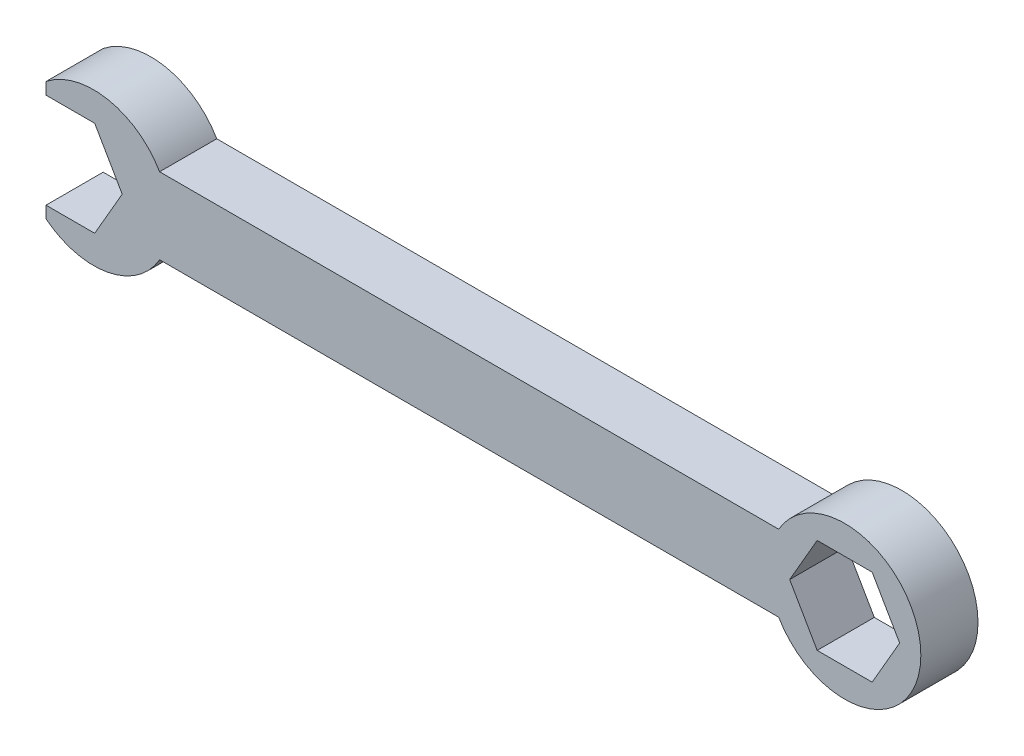
SolidWorks part; units mm, degrees
ref_plane "Front Plane" through (0, 0, 0) normal (0, 0, 1) x (1, 0, 0)
ref_plane "Top Plane" through (0, 0, 0) normal (0, 1, 0) x (1, 0, 0)
ref_plane "Right Plane" through (0, 0, 0) normal (1, 0, 0) x (0, 0, -1)
sketch "Sketch1" plane through (0, 0, 0) normal (0, 0, 1) x (1, 0, 0)
  line L0 (4.9888, 5.08) -> (87.5388, 5.08)
  line L1 (87.5388, -5.08) -> (4.9888, -5.08)
  line L2 (-10.16, 6.35) -> (-10.16, 7.9311)
  line L3 (103.67, 0) -> (100.0038, 6.35)
  line L4 (100.0038, 6.35) -> (92.6715, 6.35)
  line L5 (92.6715, 6.35) -> (89.0053, 0)
  line L6 (89.0053, 0) -> (92.6715, -6.35)
  line L7 (92.6715, -6.35) -> (100.0038, -6.35)
  line L8 (100.0038, -6.35) -> (103.67, 0)
  line L10 (-10.16, -6.35) -> (-3.6662, -6.35)
  line L11 (-3.6662, -6.35) -> (0, 0)
  line L12 (0, 0) -> (-3.6662, 6.35)
  line L13 (-3.6662, 6.35) -> (-10.16, 6.35)
  line L15 (-10.16, -6.35) -> (-10.16, -7.9311)
  line L17 (-12.8235, 3.1891) -> (-14.6472, 0.0303) [skipped]
  line L18 (-12.8212, -3.1931) -> (-10.9974, -6.352) [skipped]
  arc A0 (-10.16, -7.9311) -> (4.9888, -5.08) centre (-3.81, 0) ccw
  arc A1 (87.5388, -5.08) -> (87.5388, 5.08) centre (96.3376, 0) ccw
  circle A2 centre (96.3376, 0) radius 6.35 construction
  arc A3 (4.9888, 5.08) -> (-10.16, 7.9311) centre (-3.81, 0) ccw
  point P6 (-10.16, 7.1406)
  dimension "D1" = 20.32
  dimension "D8" = 10.16
  dimension "D2" = 12.7
  dimension "D3" = 82.55
  dimension "D4" = 10.16
  dimension "D5" = 12.7
  dimension "D6" = 6.35
  dimension "D7" = 10.16
extrude "Boss-Extrude1" add sketch "Sketch1" along normal mid plane 7.62
